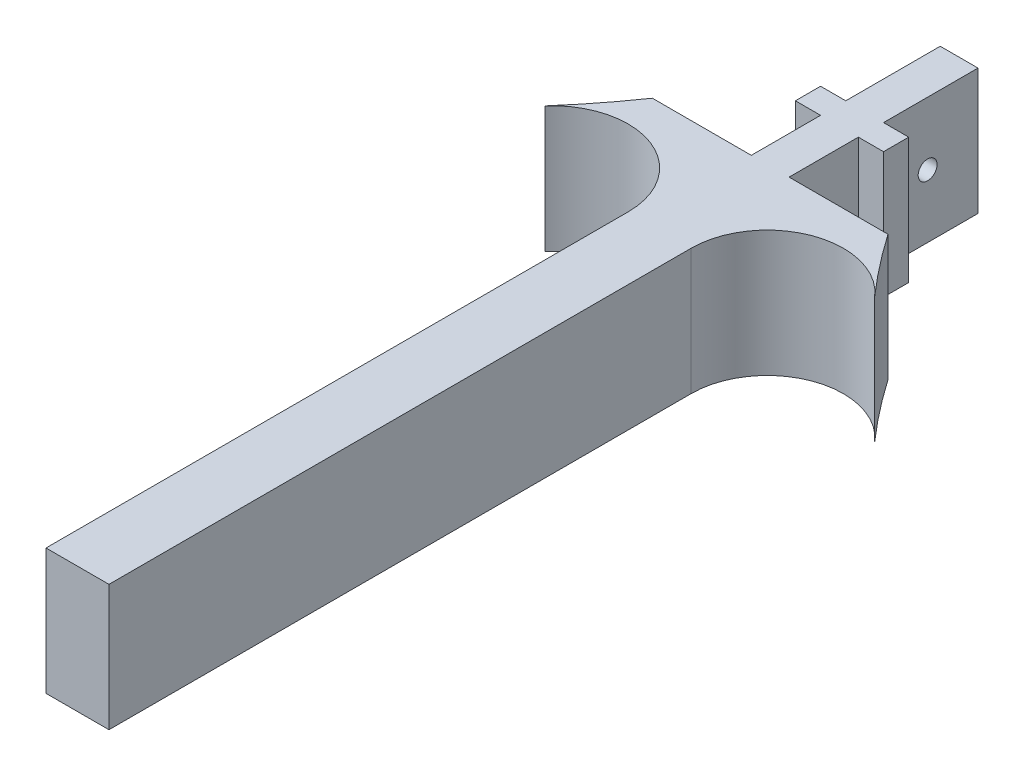
SolidWorks part; units mm, degrees
ref_plane "Plan de face" through (0, 0, 0) normal (0, 0, 1) x (1, 0, 0)
ref_plane "Plan de dessus" through (0, 0, 0) normal (0, 1, 0) x (1, 0, 0)
ref_plane "Plan de droite" through (0, 0, 0) normal (1, 0, 0) x (0, 0, -1)
sketch "Esquisse1" plane through (0, 0, 0) normal (0, 1, 0) x (1, 0, 0)
  line L0 (-3, 84.3983) -> (-3, 69.3983)
  line L1 (-3, 84.3983) -> (0, 84.3983)
  line L2 (-3, 65.3983) -> (-3, 54.3983)
  line L3 (-5, -55.6017) -> (0, -55.6017)
  line L4 (0, 84.3983) -> (0, -55.6017)
  line L5 (-3, 69.3983) -> (-7, 69.3983)
  line L6 (-3, 54.3983) -> (-18.71, 54.3983)
  line L7 (-3, 65.3983) -> (-7, 65.3983)
  line L8 (-7, 69.3983) -> (-7, 65.3983)
  line L9 (-5, 36.8425) -> (-5, -55.6017)
  arc A0 (-26.1833, 44.8157) -> (-18.71, 54.3983) centre (-105.5, 114.3795) ccw
  arc A1 (-5, 36.8425) -> (-26.1833, 44.8157) centre (-17.0922, 36.8425) ccw
  dimension "D7" = 211
  dimension "D8" = 140
  dimension "D1" = 3
  dimension "D2" = 4
  dimension "D3" = 4
  dimension "D4" = 15
  dimension "D5" = 11
  dimension "D6" = 15.71
extrude "Boss.-Extru.1" add sketch "Esquisse1" along normal blind 20
mirror "Symétrie1" about plane through (0, 20, -84.3983) normal (-1, 0, 0) of "Boss.-Extru.1"
sketch "Esquisse3" plane through (-3, 0, 0) normal (-1, 0, 0) x (0, 0, 1)
  line L2 (-84.3983, 20) -> (-69.3983, 20) construction
  line L3 (-65.3983, 20) -> (-54.3983, 20) construction
  line L4 (-84.3983, 20) -> (-84.3983, 0) construction
  circle A0 centre (-76.3983, 10) radius 1.5
  circle A1 centre (-60.3983, 10) radius 1.5
  dimension "D1" = 3
  dimension "D2" = 3
  dimension "D3" = 10
  dimension "D4" = 10
  dimension "D5" = 8
  dimension "D6" = 24
extrude "Enlèv. mat.-Extru.3" cut sketch "Esquisse3" against normal blind 20
